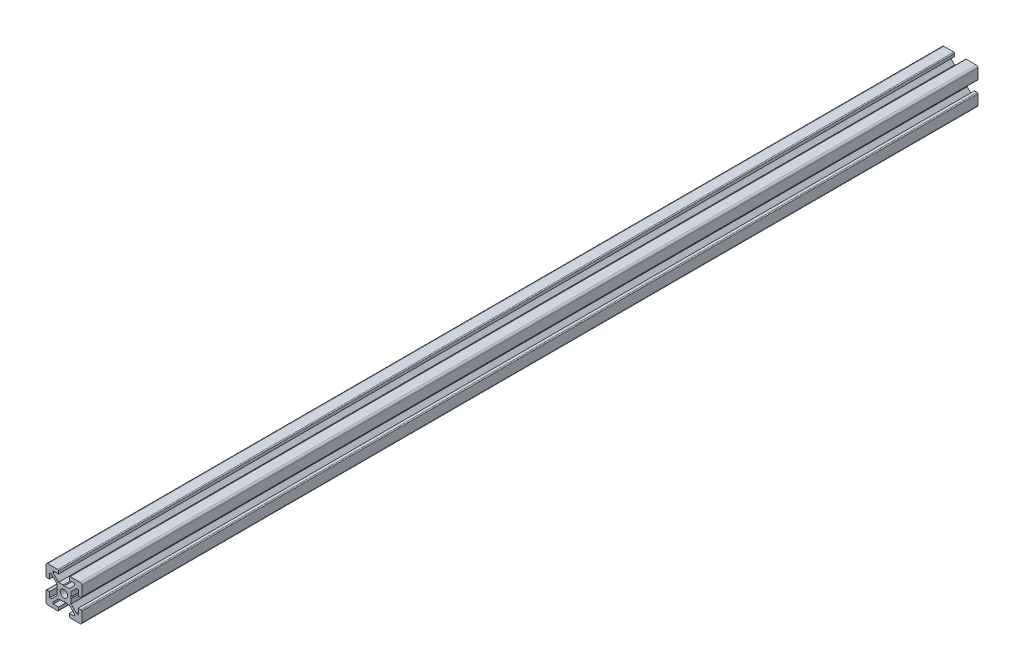
SolidWorks part; units mm, degrees
material "Lega 6061"
ref_plane "Piano frontale" through (0, 0, 0) normal (0, 0, 1) x (1, 0, 0)
ref_plane "Piano superiore" through (0, 0, 0) normal (0, 1, 0) x (1, 0, 0)
ref_plane "Piano destro" through (0, 0, 0) normal (1, 0, 0) x (0, 0, -1)
sketch "Schizzo1" plane through (0, 0, 0) normal (0, 0, 1) x (1, 0, 0)
  line L0 (0, 0) -> (-10, 0) construction
  line L1 (0, 0) -> (0, 10) construction
  line L2 (-3.6, 0) -> (-4, 0.4)
  line L3 (-4, 0.4) -> (-4, 3)
  line L4 (-4, 3) -> (-7, 6)
  line L5 (-7, 6) -> (-8, 6)
  line L6 (-8, 6) -> (-8, 3)
  line L7 (-8, 3) -> (-9.5, 3)
  line L8 (-10, 3.5) -> (-10, 9)
  line L9 (0, 0) -> (-10, 10) construction
  line L10 (0, 3.6) -> (-0.4, 4)
  line L11 (-0.4, 4) -> (-3, 4)
  line L12 (-3, 4) -> (-6, 7)
  line L13 (-6, 7) -> (-6, 8)
  line L14 (-6, 8) -> (-3, 8)
  line L15 (-3, 8) -> (-3, 9.5)
  line L16 (-3.5, 10) -> (-9, 10)
  line L17 (0, 0) -> (-10, -10) construction
  line L18 (-3.5, -10) -> (-9, -10)
  line L19 (-3, -8) -> (-3, -9.5)
  line L20 (-6, -8) -> (-3, -8)
  line L21 (-6, -7) -> (-6, -8)
  line L22 (-3, -4) -> (-6, -7)
  line L23 (-0.4, -4) -> (-3, -4)
  line L24 (0, -3.6) -> (-0.4, -4)
  line L25 (-10, -3.5) -> (-10, -9)
  line L26 (-8, -3) -> (-9.5, -3)
  line L27 (-8, -6) -> (-8, -3)
  line L28 (-7, -6) -> (-8, -6)
  line L29 (-4, -3) -> (-7, -6)
  line L30 (-4, -0.4) -> (-4, -3)
  line L31 (-3.6, 0) -> (-4, -0.4)
  line L32 (0, 0) -> (10, -10) construction
  line L33 (0, 0) -> (10, 10) construction
  line L34 (3.6, 0) -> (4, -0.4)
  line L35 (4, -0.4) -> (4, -3)
  line L36 (4, -3) -> (7, -6)
  line L37 (7, -6) -> (8, -6)
  line L38 (8, -6) -> (8, -3)
  line L39 (8, -3) -> (9.5, -3)
  line L40 (10, -3.5) -> (10, -9)
  line L41 (0, -3.6) -> (0.4, -4)
  line L42 (0.4, -4) -> (3, -4)
  line L43 (3, -4) -> (6, -7)
  line L44 (6, -7) -> (6, -8)
  line L45 (6, -8) -> (3, -8)
  line L46 (3, -8) -> (3, -9.5)
  line L47 (3.5, -10) -> (9, -10)
  line L48 (3.5, 10) -> (9, 10)
  line L49 (3, 8) -> (3, 9.5)
  line L50 (6, 8) -> (3, 8)
  line L51 (6, 7) -> (6, 8)
  line L52 (3, 4) -> (6, 7)
  line L53 (0.4, 4) -> (3, 4)
  line L54 (0, 3.6) -> (0.4, 4)
  line L55 (10, 3.5) -> (10, 9)
  line L56 (8, 3) -> (9.5, 3)
  line L57 (8, 6) -> (8, 3)
  line L58 (7, 6) -> (8, 6)
  line L59 (4, 3) -> (7, 6)
  line L60 (4, 0.4) -> (4, 3)
  line L61 (3.6, 0) -> (4, 0.4)
  arc A0 (-10, 9) -> (-9, 10) centre (-9, 9) cw
  arc A1 (-3, 9.5) -> (-3.5, 10) centre (-3.5, 9.5) ccw
  arc A2 (-9.5, 3) -> (-10, 3.5) centre (-9.5, 3.5) cw
  arc A3 (-9.5, -3) -> (-10, -3.5) centre (-9.5, -3.5) ccw
  arc A4 (-3, -9.5) -> (-3.5, -10) centre (-3.5, -9.5) cw
  arc A5 (-10, -9) -> (-9, -10) centre (-9, -9) ccw
  arc A6 (10, -9) -> (9, -10) centre (9, -9) cw
  arc A7 (3, -9.5) -> (3.5, -10) centre (3.5, -9.5) ccw
  arc A8 (9.5, -3) -> (10, -3.5) centre (9.5, -3.5) cw
  arc A9 (9.5, 3) -> (10, 3.5) centre (9.5, 3.5) ccw
  arc A10 (3, 9.5) -> (3.5, 10) centre (3.5, 9.5) cw
  arc A11 (10, 9) -> (9, 10) centre (9, 9) ccw
  circle A12 centre (0, 0) radius 2.1
  point P24 (-3, 10)
  point P27 (-10, 3)
  point P49 (-10, -3)
  point P50 (-3, -10)
  point P92 (3, -10)
  point P93 (10, -3)
  point P94 (10, 3)
  point P95 (3, 10)
  dimension "D2" = 1
  dimension "D12" = 0.5
  dimension "D13" = 4.2
  dimension "D3" = 8
  dimension "D4" = 0.4
  dimension "D5" = 45
  dimension "D6" = 6
  dimension "D7" = 12
  dimension "D8" = 20
  dimension "D9" = 2
  dimension "D10" = 4
  dimension "D11" = 45
extrude "Estrusione-Estrusione1" add sketch "Schizzo1" along normal blind 500
sketch "Schizzo2" plane through (-10, 0, 0) normal (-1, 0, 0) x (0, 0, 1)
  line L0 (500, 0) -> (0, 0) construction
  line L1 (0, -3.5) -> (0, -9) construction
  line L2 (250, 0.4) -> (250, 18.0033) construction
  line L3 (500, 0.4) -> (0, 0.4) construction
  circle A0 centre (25, 0) radius 4
  circle A1 centre (475, 0) radius 4
  dimension "D2" = 8
  dimension "D1" = 25
